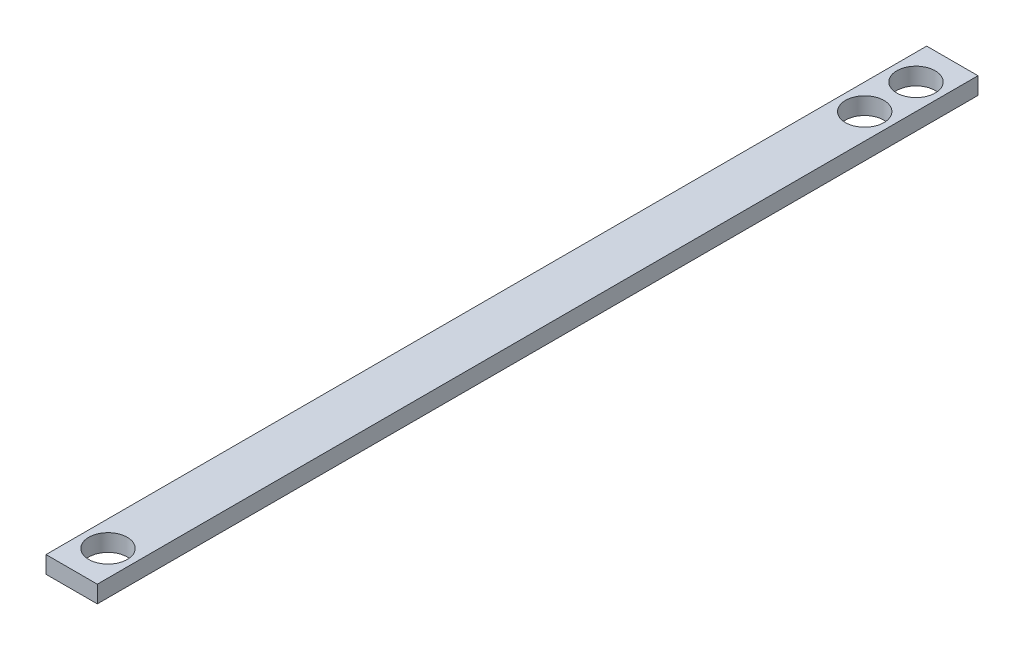
SolidWorks part; units mm, degrees
ref_plane "Front Plane" through (0, 0, 0) normal (0, 0, 1) x (1, 0, 0)
ref_plane "Top Plane" through (0, 0, 0) normal (0, 1, 0) x (1, 0, 0)
ref_plane "Right Plane" through (0, 0, 0) normal (1, 0, 0) x (0, 0, -1)
sketch "Sketch1" plane through (0, 0, 0) normal (0, 0, 1) x (1, 0, 0)
  line L1 (0, 0) -> (38.1, 0)
  line L2 (0, 0) -> (0, 12.7)
  line L3 (0, 12.7) -> (38.1, 12.7)
  line L4 (38.1, 0) -> (38.1, 12.7)
  dimension "D1" = 12.7
  dimension "D2" = 38.1
extrude "Boss-Extrude1" add sketch "Sketch1" along normal blind 615.95
sketch "Sketch2" plane through (0, 12.7, 0) normal (0, 1, 0) x (1, 0, 0)
  line L0 (38.1, -615.95) -> (0, -615.95) construction
  line L2 (38.1, 0) -> (0, 0) construction
  circle A0 centre (19.05, -588.9498) radius 14.3002
  circle A1 centre (19.05, -27.0002) radius 14.3002
  point P4 (0, 0)
  point P8 (0, 0)
  point P11 (19.05, 0)
  dimension "D1" = 28.6004
  dimension "D4" = 28.6004
  dimension "D2" = 27.0002
  dimension "D5" = 27.0002
extrude "Cut-Extrude1" cut sketch "Sketch2" against normal blind 762
sketch "Sketch3" plane through (0, 0, 0) normal (0, 0, -1) x (-1, 0, 0)
  line L1 (-38.1, 12.7) -> (0, 12.7)
  line L2 (-38.1, 12.7) -> (-38.1, 0)
  line L3 (-38.1, 0) -> (0, 0)
  line L4 (0, 12.7) -> (0, 0)
extrude "Boss-Extrude2" add sketch "Sketch3" along normal blind 38.1
sketch "Sketch4" plane through (0, 12.7, 0) normal (0, 1, 0) x (1, 0, 0)
  line L0 (0, 38.1) -> (38.1, 38.1) construction
  circle A0 centre (19.05, 11.0998) radius 14.3002
  point P4 (0, 0)
  point P5 (19.05, 38.1)
  dimension "D1" = 28.6004
  dimension "D2" = 27.0002
extrude "Cut-Extrude2" cut sketch "Sketch4" against normal blind 101.6
